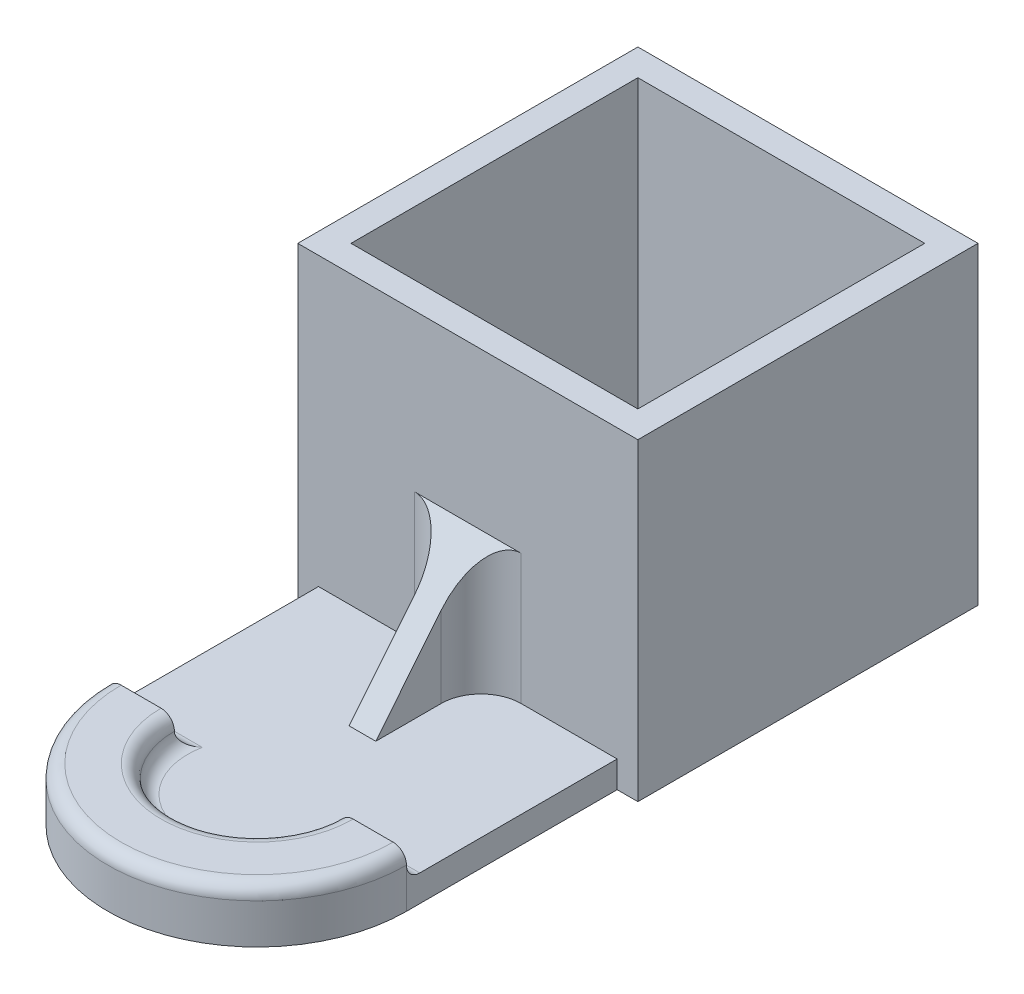
SolidWorks part; units mm, degrees
ref_plane "Front Plane" through (0, 0, 0) normal (0, 0, 1) x (1, 0, 0)
ref_plane "Top Plane" through (0, 0, 0) normal (0, 1, 0) x (1, 0, 0)
ref_plane "Right Plane" through (0, 0, 0) normal (1, 0, 0) x (0, 0, -1)
sketch "Sketch1" plane through (0, 0, 0) normal (0, 1, 0) x (1, 0, 0)
  line L1 (0, 0) -> (21.5443, 0)
  line L2 (0, 0) -> (0, 21.5443)
  line L3 (0, 21.5443) -> (21.5443, 21.5443)
  line L4 (21.5443, 0) -> (21.5443, 21.5443)
  dimension "D1" = 21.5443
extrude "Extrude-Thin1" add sketch "Sketch1" along normal blind 21.5443 thin thin type one direction wall 2
sketch "Sketch2" plane through (0, 0, 0) normal (0, -1, 0) x (1, 0, 0)
  line L4 (-2, 2) -> (-2, -23.5443)
  line L5 (-2, -23.5443) -> (23.5443, -23.5443)
  line L6 (23.5443, -23.5443) -> (23.5443, 2)
  line L7 (23.5443, 2) -> (-2, 2)
  line L8 (-2, 2) -> (-2, -23.5443)
  line L9 (-2, -23.5443) -> (23.5443, -23.5443)
  line L10 (23.5443, -23.5443) -> (23.5443, 2)
  line L11 (23.5443, 2) -> (-2, 2)
  dimension "D1" = 0
extrude "Boss-Extrude1" add sketch "Sketch2" along normal blind 2
sketch "Sketch4" plane through (0, -2, 0) normal (0, -1, 0) x (1, 0, 0)
  line L0 (10.7722, 2) -> (10.7722, 17.8236) construction
  line L1 (23.5443, 2) -> (-2, 2) construction
  line L2 (-0.4433, 2) -> (-0.4433, 17.8236)
  line L3 (21.9876, 2) -> (21.9876, 17.8236)
  arc A0 (-0.4433, 2) -> (21.9876, 2) centre (10.7722, 2) ccw
  arc A1 (21.9876, 17.8236) -> (-0.4433, 17.8236) centre (10.7722, 17.8236) ccw
  point P4 (10.7722, 9.9118)
  point P9 (2.3208, 17.8236)
extrude "Boss-Extrude2" add sketch "Sketch4" against normal blind 2
ref_plane "Plane1" through (10.7722, 0, 0) normal (1, 0, 0) x (0, 0, -1)
sketch "Sketch5" plane through (10.7722, 0, 0) normal (1, 0, 0) x (0, 0, -1)
  line L0 (-2, 9.7722) -> (-9.9118, 0)
  line L1 (-2, 21.5443) -> (-2, -2) construction
  line L2 (-2, 0) -> (-17.8236, 0) construction
  line L3 (-2, 9.7722) -> (-2, 0)
  line L4 (-2, 0) -> (-9.9118, 0)
extrude "Boss-Extrude3" add sketch "Sketch5" along normal mid plane 2
fillet "Fillet2" radius 3 2 edges at (11.7722, 4.8861, 2) (9.7722, 4.8861, 2)
sketch "Sketch6" plane through (0, 0, 0) normal (0, 1, 0) x (1, 0, 0)
  arc A0 (-0.4433, -17.8236) -> (21.9876, -17.8236) centre (10.7722, -17.8236) ccw construction
  arc A1 (-0.4433, -17.8236) -> (21.9876, -17.8236) centre (10.7722, -17.8236) ccw
extrude "Extrude-Thin2" add sketch "Sketch6" along normal blind 2 thin thin type one direction reverse wall 5
fillet "Fillet3" radius 1 5 edges at (19.4876, 0, 17.8236) (2.0567, 0, 17.8236) (10.7722, 2, 29.039) (10.7722, 2, 24.039) (10.7722, 0, 24.039)
